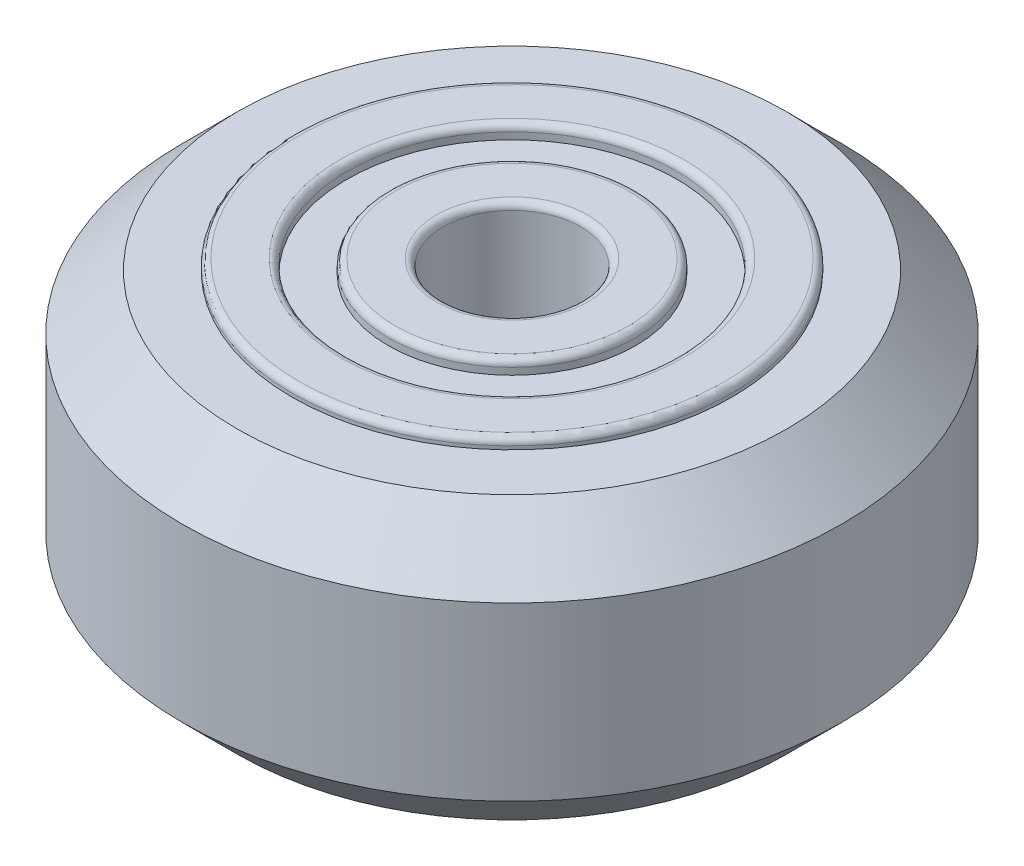
SolidWorks part; units mm, degrees
ref_plane "Front Plane" through (0, 0, 0) normal (0, 0, 1) x (1, 0, 0)
ref_plane "Top Plane" through (0, 0, 0) normal (0, 1, 0) x (1, 0, 0)
ref_plane "Right Plane" through (0, 0, 0) normal (1, 0, 0) x (0, 0, -1)
sketch "Sketch2" plane through (0, 0, 0) normal (0, 1, 0) x (1, 0, 0)
  circle A0 centre (0, 0) radius 12
  circle A1 centre (0, 0) radius 8
  circle A2 centre (0, 0) radius 2.5
  circle A3 centre (0, 0) radius 4.5
  circle A4 centre (0, 0) radius 6
  dimension "D1" = 24
  dimension "D2" = 16
  dimension "D3" = 5
  dimension "D4" = 9
  dimension "D5" = 12
extrude "Boss-Extrude1" add sketch "Sketch2" along normal mid plane 10.25 contours A0 A1 region at (-11.6606, 0, 0)
extrude "Boss-Extrude2" add sketch "Sketch2<3>" along normal mid plane 11 separate body contours A1 A4 | A3 A2 region at (-7.7737, 0, 0) region at (-4.3727, 0, 0)
sketch "Sketch2<3>" plane through (0, 0, 0) normal (0, 1, 0) x (1, 0, 0) same geometry as "Sketch2"
extrude "Boss-Extrude3" add sketch "Sketch2<5>" along normal mid plane 10 contours A4 A3 region at (-5.8303, 0, 0)
sketch "Sketch2<5>" plane through (0, 0, 0) normal (0, 1, 0) x (1, 0, 0) same geometry as "Sketch2"
chamfer "Chamfer1" distance 2 angle 45 2 edges at (0, -5.125, 12) (0, 5.125, 12)
fillet "Fillet1" radius 0.25 8 edges at (0, -5.5, 4.5) (0, -5.5, 2.5) (0, 5.5, 4.5) (0, 5.5, 2.5) (0, 5.5, 8) (0, 5.5, 6) (0, -5.5, 8) (0, -5.5, 6)
